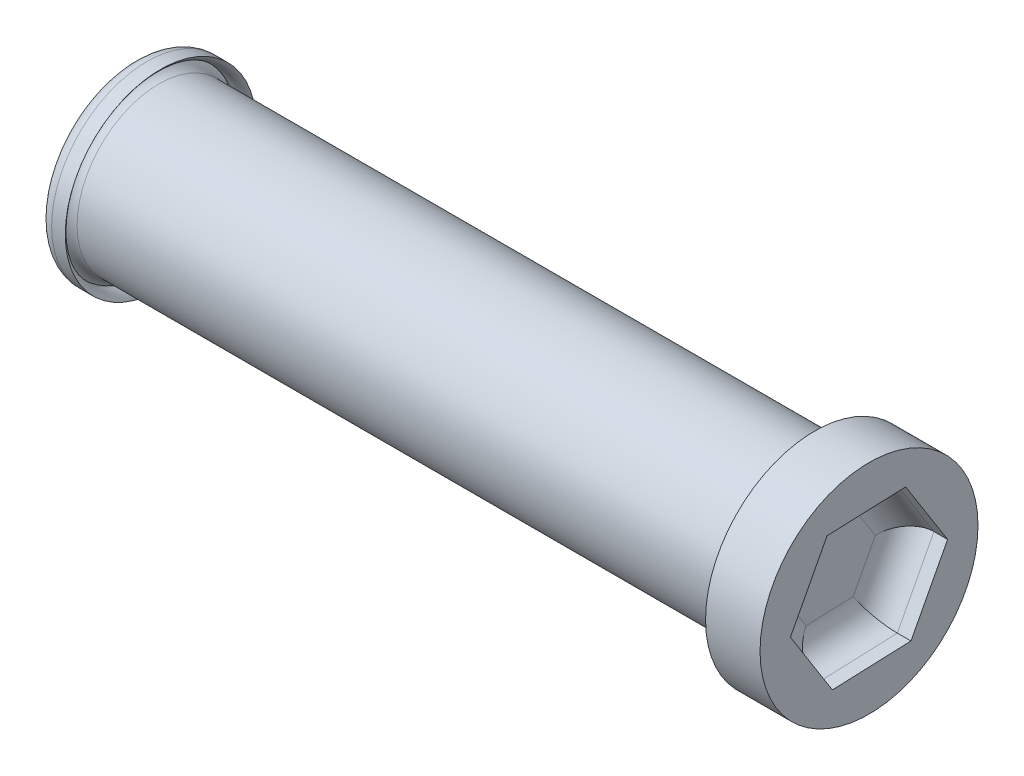
SolidWorks part; units mm, degrees
ref_plane "Plano frontal" through (0, 0, 0) normal (0, 0, 1) x (1, 0, 0)
ref_plane "Plano superior" through (0, 0, 0) normal (0, 1, 0) x (1, 0, 0)
ref_plane "Plano direito" through (0, 0, 0) normal (1, 0, 0) x (0, 0, -1)
sketch "Esboço1" plane through (0, 0, 0) normal (0, 0, 1) x (1, 0, 0)
  line L1 (0, 0) -> (0, 4)
  line L2 (0, 4) -> (2, 4)
  line L3 (2, 4) -> (2, 0)
  line L4 (2, 0) -> (0, 0)
  dimension "D2" = 4
  dimension "D3" = 2
revolve "Revolução3" add sketch "Esboço1" angle 360 about L4
sketch "Esboço4" plane through (0, 0, 0) normal (-1, 0, 0) x (0, 0, 1)
  circle A0 centre (0, 0) radius 3
  dimension "D1" = 6
extrude "Ressalto-extrusão1" add sketch "Esboço4" along normal blind 24
sketch "Esboço5" plane through (2, 0, 0) normal (1, 0, 0) x (0, 0, -1)
  line L1 (1.3445, 2.5545) -> (-1.54, 2.4416)
  line L2 (-1.54, 2.4416) -> (-2.8845, -0.1129)
  line L3 (-2.8845, -0.1129) -> (-1.3445, -2.5545)
  line L4 (-1.3445, -2.5545) -> (1.54, -2.4416)
  line L5 (1.54, -2.4416) -> (2.8845, 0.1129)
  line L6 (2.8845, 0.1129) -> (1.3445, 2.5545)
  circle A0 centre (0, 0) radius 2.5 construction
  dimension "D1" = 5
extrude "Corte-extrusão1" cut sketch "Esboço5" against normal blind 1.5
sketch "Esboço6" plane through (-24, 0, 0) normal (-1, 0, 0) x (0, 0, 1)
  circle A0 centre (0, 0) radius 3.5
  dimension "D1" = 7
extrude "Ressalto-extrusão2" add sketch "Esboço6" along normal blind 1
sketch "Esboço7" plane through (-25, 0, 0) normal (-1, 0, 0) x (0, 0, 1)
  circle A0 centre (0, 0) radius 2.5
  dimension "D1" = 5
extrude "Corte-extrusão2" cut sketch "Esboço7" against normal blind 1
sketch "Esboço8" plane through (-24, 0, 0) normal (1, 0, 0) x (0, 0, -1)
  circle A0 centre (0, 0) radius 3.25
  circle A1 centre (0, 0) radius 3
  dimension "D1" = 6.5
extrude "Corte-extrusão3" cut sketch "Esboço8" against normal blind 0.5
fillet "Filete2" radius 0.5 5 edges at (-24.5, 0, -3) (0, 0, -3) (-24, 0, 2.5) (-25, 0, 3.5) (-24, 0, -3.25)
fillet "Filete3" radius 1 6 edges at (0.5, -1.1644, -2.2123) (0.5, -2.4981, -0.0978) (0.5, -1.3337, 2.1145) (0.5, 1.1644, 2.2123) (0.5, 2.4981, 0.0978) (0.5, 1.3337, -2.1145)
